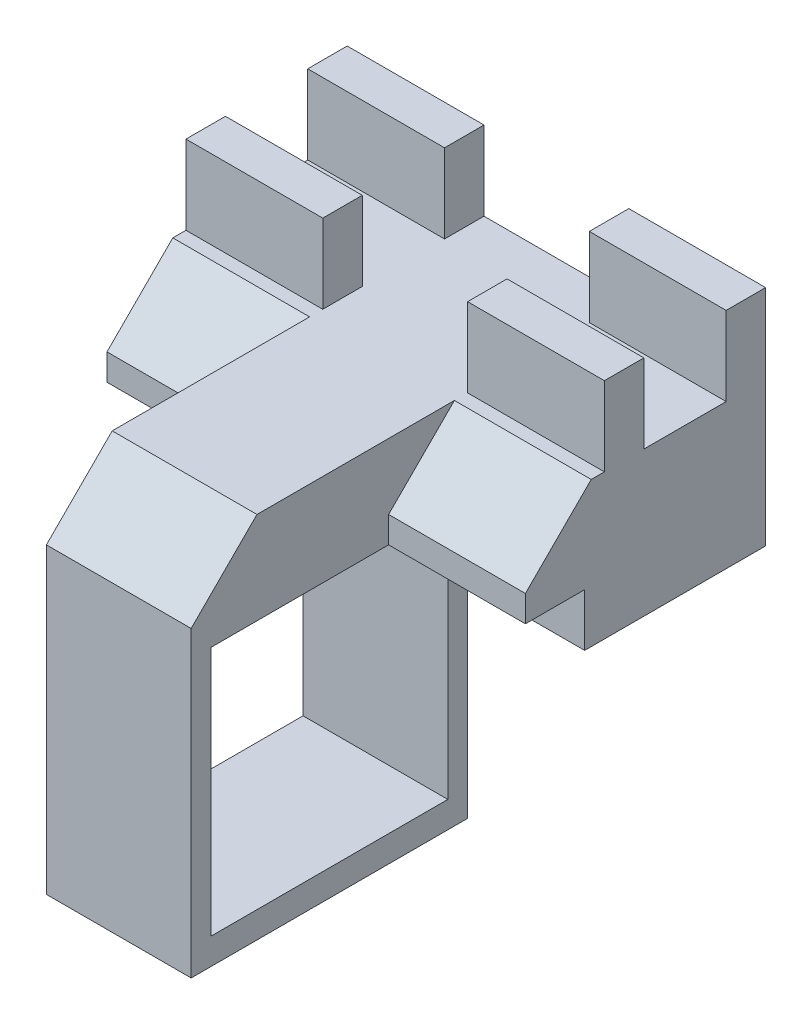
SolidWorks part; units mm, degrees
note: '?' marks a value the reader was unsure of. The reader was unsure of these and kept them because the rebuilt part matched: shared geometry of "Sketch1<3>", "Sketch1<6>".
ref_plane "Vehicle Ground Plane" through (0, 0, 0) normal (0, 0, 1) x (1, 0, 0)
ref_plane "Vehicle Centreline Plane" through (0, 0, 0) normal (0, 1, 0) x (1, 0, 0)
ref_plane "Front Roll Hoop Plane" through (0, 0, 0) normal (1, 0, 0) x (0, 0, -1)
ref_axis "X-Axis" through (-88.99, 0, 0) along (1, 0, 0)?
ref_axis "Y-Axis" through (0, 55, 0) along (0, -1, 0)?
ref_axis "Z-Axis" through (0, 0, -88.99) along (0, 0, 1)?
sketch "Sketch1" plane through (0, 0, 0) normal (0, 1, 0) x (1, 0, 0)
  line L0 (0.9451, 0) -> (0.9451, -12.5)
  line L5 (1.8901, 0) -> (0, 0)
  line L6 (0.9451, -12.5) -> (21.735, -12.5)
  line L7 (0.9451, -12.5) -> (0.9451, -18.5)
  line L8 (32.735, -18.5) -> (32.735, -60.5)
  line L9 (0.9451, -18.5) -> (0.9451, -30.5)
  line L10 (0.9451, 0) -> (21.735, 0)
  line L11 (-55, 0) -> (55, 0) construction
  line L12 (21.735, 0) -> (21.735, -18.5)
  line L13 (21.735, -18.5) -> (0.9451, -18.5)
  line L14 (0.9451, 0) -> (0.9451, 6)
  line L15 (0.9451, 6) -> (21.735, 6)
  line L16 (21.735, 6) -> (21.735, 0)
  line L17 (0.9451, -18.5) -> (21.735, -18.5)
  line L18 (0.9451, -30.5) -> (21.735, -30.5)
  line L19 (21.735, -30.5) -> (21.735, -18.5)
  line L20 (21.735, -18.5) -> (21.735, 6)
  line L21 (0.9451, 6) -> (0.9451, -18.5)
  line L22 (21.735, -30.5) -> (21.735, -60.5)
  line L23 (21.735, -60.5) -> (43.735, -60.5)
  line L24 (43.735, -60.5) -> (43.735, -30.5)
  line L25 (43.735, -30.5) -> (43.735, -18.5)
  line L26 (21.735, -18.5) -> (43.735, -18.5)
  line L27 (43.735, -30.5) -> (43.735, -18.5)
  line L28 (43.735, 0) -> (43.735, -18.5)
  line L29 (64.525, -12.5) -> (43.735, -12.5)
  line L30 (43.735, -18.5) -> (64.525, -18.5)
  line L31 (64.525, -30.5) -> (43.735, -30.5)
  line L32 (64.525, 6) -> (43.735, 6)
  line L33 (43.735, 6) -> (43.735, 0)
  line L34 (64.525, 6) -> (64.525, -18.5)
  line L35 (64.525, 0) -> (64.525, 6)
  line L36 (64.525, -18.5) -> (64.525, -30.5)
  line L37 (64.525, -12.5) -> (64.525, -18.5)
  line L38 (64.525, 0) -> (64.525, -12.5)
  line L39 (43.735, 0) -> (64.525, 0)
  point P6 (0.9451, 0)
  point P31 (64.525, 0)
  point P32 (0, 0)
  point P33 (0, 0)
  point P34 (0, 0)
  point P35 (0, 0)
  point P36 (0, 0)
  point P37 (0, 0)
  dimension "D1" = 12.5
  dimension "D2" = 6
  dimension "D3" = 12
  dimension "D4" = 6
  dimension "D5" = 30
  dimension "D6" = 22
  dimension "D7" = 20.79
  dimension "D8" = 0.9451
extrude "Boss-Extrude2" add sketch "Sketch1" along normal blind 23 contours L16 L15 L14 L5 L10 | L13 L12 L6 L7 | L34 L29 L28 L30 | L33 L39 L34 L32
extrude "Boss-Extrude3" add sketch "Sketch1<3>" against normal blind 11 contours L13 L12 L6 L7 | L12 L10 L5 L0 L6 | L16 L15 L14 L5 L10 | L39 L28 L29 L34 | L36 L30 L25 L31 | L34 L29 L28 L30 | L33 L39 L34 L32
sketch "Sketch1<3>" plane through (0, 0, 0) normal (0, 1, 0) x (1, 0, 0) same geometry as "Sketch1"
extrude "Boss-Extrude5" add sketch "Sketch1<6>" against normal blind 45 contours L26 L8 L23 L24 L25 | L26 L19 L22 L23 L8
sketch "Sketch1<6>" plane through (0, 0, 0) normal (0, 1, 0) x (1, 0, 0) same geometry as "Sketch1"
ref_plane "Plane1" through (74.525, 0, 0) normal (1, 0, 0) x (0, 0, -1)
sketch "Sketch2" plane through (74.525, 0, 0) normal (1, 0, 0) x (0, 0, -1)
  line L0 (6, 0) -> (-30.5, 0) construction
  line L1 (-30.5, 0) -> (-30.5, -11) construction
  line L2 (-30.5, -11) -> (6, -11) construction
  line L3 (6, -11) -> (6, 0) construction
  line L4 (-18.5, -45) -> (-18.5, -11) construction
  line L5 (-18.5, -11) -> (-30.5, -11) construction
  line L6 (-30.5, -11) -> (-30.5, 0) construction
  line L7 (-30.5, 0) -> (-60.5, 0) construction
  line L8 (-60.5, 0) -> (-60.5, -45) construction
  line L9 (-60.5, -45) -> (-18.5, -45) construction
  line L10 (6, 0) -> (-30.5, 0)
  line L11 (-30.5, 0) -> (-30.5, -11)
  line L12 (-30.5, -11) -> (6, -11)
  line L13 (6, -11) -> (6, 0)
  line L14 (-18.5, -45) -> (-18.5, -11)
  line L15 (-18.5, -11) -> (-30.5, -11)
  line L16 (-30.5, -11) -> (-30.5, 0)
  line L17 (-30.5, 0) -> (-60.5, 0)
  line L18 (-60.5, 0) -> (-60.5, -45)
  line L19 (-60.5, -45) -> (-18.5, -45)
  line L20 (-60.5, -14.9897) -> (-57.5, -14.9897)
  line L21 (-34.5516, -45) -> (-34.5516, -42)
  line L22 (-41.1839, 0) -> (-41.1839, -3)
  line L23 (-57.5, -41) -> (-21.5, -41)
  line L24 (-57.5, -41) -> (-57.5, -3)
  line L25 (-57.5, -3) -> (-21.5, -3)
  line L26 (-21.5, -41) -> (-21.5, -3)
  dimension "D1" = 3
  dimension "D2" = 3
  dimension "D3" = 3
  dimension "D4" = 3
  dimension "D5" = 38
  dimension "D6" = 36
extrude "Cut-Extrude1" cut sketch "Sketch2" against normal through all contours L23 L26 L12 L16 L25 L24 | L12 L26 L25 L16
sketch "Sketch3" plane through (43.735, 0, 0) normal (-1, 0, 0) x (0, 0, 1)
  line L1 (-6, 0) -> (18.5, 0)
  line L2 (-6, 0) -> (-6, -11)
  line L3 (-6, -11) -> (18.5, -11)
  line L4 (18.5, 0) -> (18.5, -11)
extrude "Boss-Extrude6" add sketch "Sketch3" along normal blind 42
sketch "Sketch4" plane through (0, 0, 0) normal (0, 1, 0) x (1, 0, 0)
  line L0 (0.9451, -18.5) -> (64.525, -18.5)
  line L20 (64.525, -18.5) -> (43.735, -18.5)
  line L21 (43.735, -18.5) -> (43.735, -12.5)
  line L22 (43.735, -12.5) -> (64.525, -12.5)
  line L23 (64.525, -12.5) -> (64.525, 0)
  line L24 (64.525, 0) -> (43.735, 0)
  line L25 (43.735, 0) -> (43.735, 6)
  line L26 (43.735, 6) -> (21.735, 6)
  line L27 (21.735, 6) -> (21.735, 0)
  line L28 (21.735, 0) -> (0.9451, 0)
  line L29 (0.9451, 0) -> (0.9451, -12.5)
  line L30 (0.9451, -12.5) -> (21.735, -12.5)
  line L31 (21.735, -12.5) -> (21.735, -18.5)
  line L32 (21.735, -18.5) -> (0.9451, -18.5)
  line L33 (0.9451, -18.5) -> (0.9451, -30.5)
  line L34 (0.9451, -30.5) -> (21.735, -30.5)
  line L35 (21.735, -30.5) -> (21.735, -60.5)
  line L36 (21.735, -60.5) -> (43.735, -60.5)
  line L37 (43.735, -60.5) -> (43.735, -30.5)
  line L38 (43.735, -30.5) -> (64.525, -30.5)
  line L39 (64.525, -30.5) -> (64.525, -18.5)
  line L40 (64.525, -18.5) -> (43.735, -18.5)
  line L41 (43.735, -18.5) -> (43.735, -12.5)
  line L42 (43.735, -12.5) -> (64.525, -12.5)
  line L43 (64.525, -12.5) -> (64.525, 0)
  line L44 (64.525, 0) -> (43.735, 0)
  line L45 (43.735, 0) -> (43.735, 6)
  line L46 (43.735, 6) -> (21.735, 6)
  line L47 (21.735, 6) -> (21.735, 0)
  line L48 (21.735, 0) -> (0.9451, 0)
  line L49 (0.9451, 0) -> (0.9451, -12.5)
  line L50 (0.9451, -12.5) -> (21.735, -12.5)
  line L51 (21.735, -12.5) -> (21.735, -18.5)
  line L52 (21.735, -18.5) -> (0.9451, -18.5)
  line L53 (0.9451, -18.5) -> (0.9451, -30.5)
  line L54 (0.9451, -30.5) -> (21.735, -30.5)
  line L55 (21.735, -30.5) -> (21.735, -60.5)
  line L56 (21.735, -60.5) -> (43.735, -60.5)
  line L57 (43.735, -60.5) -> (43.735, -30.5)
  line L58 (43.735, -30.5) -> (64.525, -30.5)
  line L59 (64.525, -30.5) -> (64.525, -18.5)
  dimension "D1" = 0
extrude "Boss-Extrude7" add sketch "Sketch4" along normal blind 11 contours L40 L41 L42 L43 L44 L45 L46 L47 L48 L49 L50 L51 L52 L53 L54 L55 L56 L57 L58 L59
chamfer "Chamfer2" distance 10 angle 45 3 edges at (32.735, 11, 60.5) (54.13, 11, 30.5) (11.3401, 11, 30.5)
equation "\"x-bitch\"=12"
equation "\"D3@Sketch1\"=\"x-bitch\""
